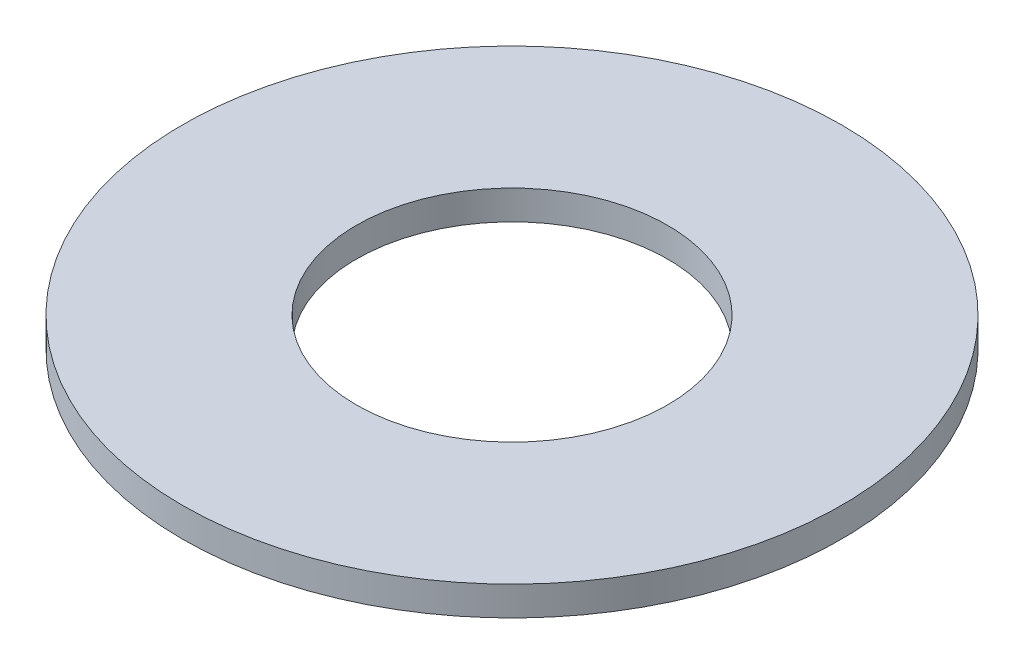
SolidWorks part; units mm, degrees
ref_plane "Front Plane" through (0, 0, 0) normal (0, 0, 1) x (1, 0, 0)
ref_plane "Top Plane" through (0, 0, 0) normal (0, 1, 0) x (1, 0, 0)
ref_plane "Right Plane" through (0, 0, 0) normal (1, 0, 0) x (0, 0, -1)
sketch "Sketch1" plane through (0, 0, 0) normal (0, 1, 0) x (1, 0, 0)
  circle A0 centre (0, 0) radius 90
  dimension "FLANGE_OD" = 180
extrude "Boss-Extrude1" add sketch "Sketch1" along normal blind 8
sketch "Sketch2" plane through (0, 0, 0) normal (0, 1, 0) x (1, 0, 0)
  circle A0 centre (0, 0) radius 42.5
  dimension "BORE_D" = 85
extrude "Cut-Extrude1" cut sketch "Sketch2" along normal through all
sketch "Sketch3" plane through (0, 8, 0) normal (0, 1, 0) x (1, 0, 0)
  circle A0 centre (0, 0) radius 32.7893 construction
  circle A1 centre (-32.7893, 0) radius 5.4361
  dimension "BOLT_D" = 10.8722
  dimension "BOLT_PCD" = 65.5785
extrude "Cut-Extrude2" cut sketch "Sketch3" against normal blind 5.2595 rebuild error yes
pattern_circular "CirPattern1" count 8 over 360 rebuild error yes
